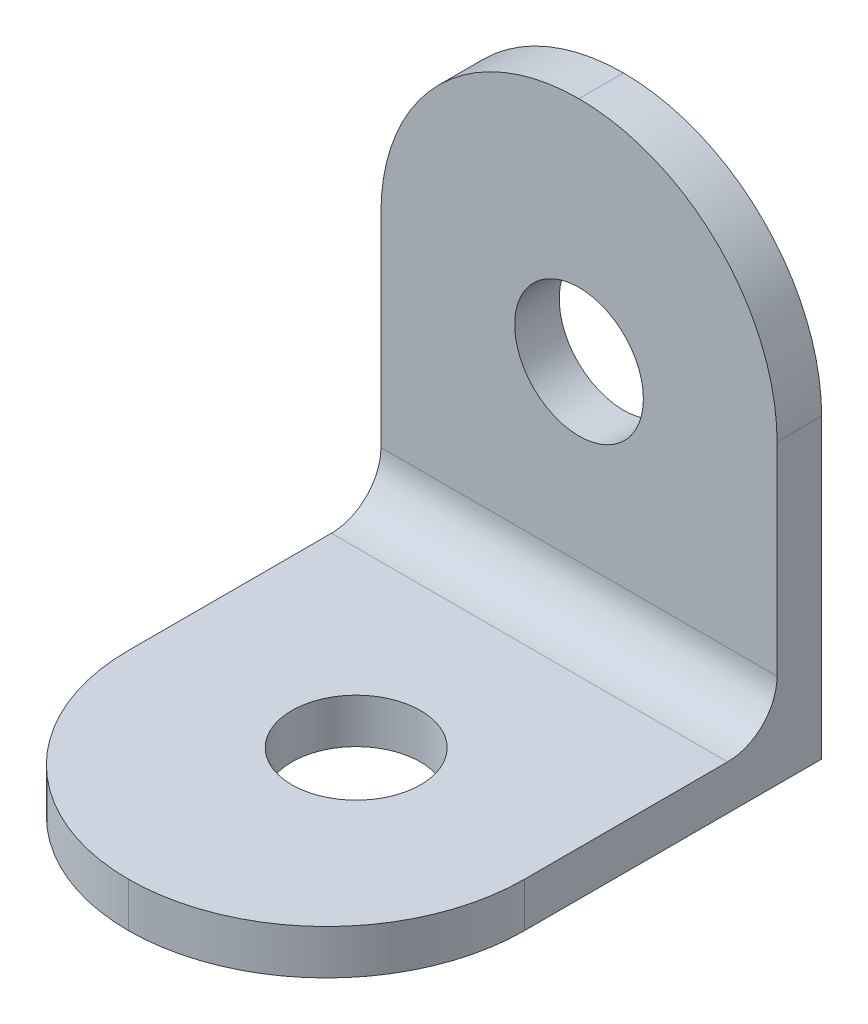
SolidWorks part; units mm, degrees
ref_plane "Front Plane" through (0, 0, 0) normal (0, 0, 1) x (1, 0, 0)
ref_plane "Top Plane" through (0, 0, 0) normal (0, 1, 0) x (1, 0, 0)
ref_plane "Right Plane" through (0, 0, 0) normal (1, 0, 0) x (0, 0, -1)
sketch "Sketch1" plane through (0, 0, 0) normal (0, 0, 1) x (1, 0, 0)
  line L1 (0, 0) -> (16, 0)
  line L2 (0, 0) -> (0, 20)
  line L3 (0, 20) -> (16, 20)
  line L4 (16, 0) -> (16, 20)
  dimension "D1" = 16
  dimension "D2" = 20
extrude "Boss-Extrude1" add sketch "Sketch1" along normal blind 1.8
sketch "Sketch2" plane through (0, 0, 0) normal (0, -1, 0) x (1, 0, 0)
  line L1 (0, 1.8) -> (16, 1.8)
  line L2 (0, 1.8) -> (0, 20)
  line L3 (0, 20) -> (16, 20)
  line L4 (16, 1.8) -> (16, 20)
  dimension "D1" = 18.2
  dimension "D2" = 16
extrude "Boss-Extrude2" add sketch "Sketch2" against normal blind 1.8
sketch "Sketch3" plane through (0, 0, 1.8) normal (0, 0, 1) x (1, 0, 0)
  line L0 (16, 1.8) -> (16, 20) construction
  line L1 (0, 1.8) -> (16, 1.8) construction
  circle A0 centre (8, 10.8) radius 2.6
  dimension "D1" = 5.2
  dimension "D2" = 8
  dimension "D3" = 9
extrude "Cut-Extrude1" cut sketch "Sketch3" against normal blind 1.8
sketch "Sketch4" plane through (0, 1.8, 0) normal (0, 1, 0) x (1, 0, 0)
  line L0 (16, -1.8) -> (16, -20) construction
  line L2 (16, -1.8) -> (0, -1.8) construction
  circle A0 centre (8, -10.8) radius 2.6
  dimension "D1" = 8
  dimension "D2" = 5.2
  dimension "D3" = 9
extrude "Cut-Extrude2" cut sketch "Sketch4" against normal blind 1.8
fillet "Fillet1" radius 2 1 edges at (8, 1.8, 1.8)
fillet "Fillet2" radius 8 4 edges at (16, 0.9, 20) (0, 0.9, 20) (16, 20, 0.9) (0, 20, 0.9)
